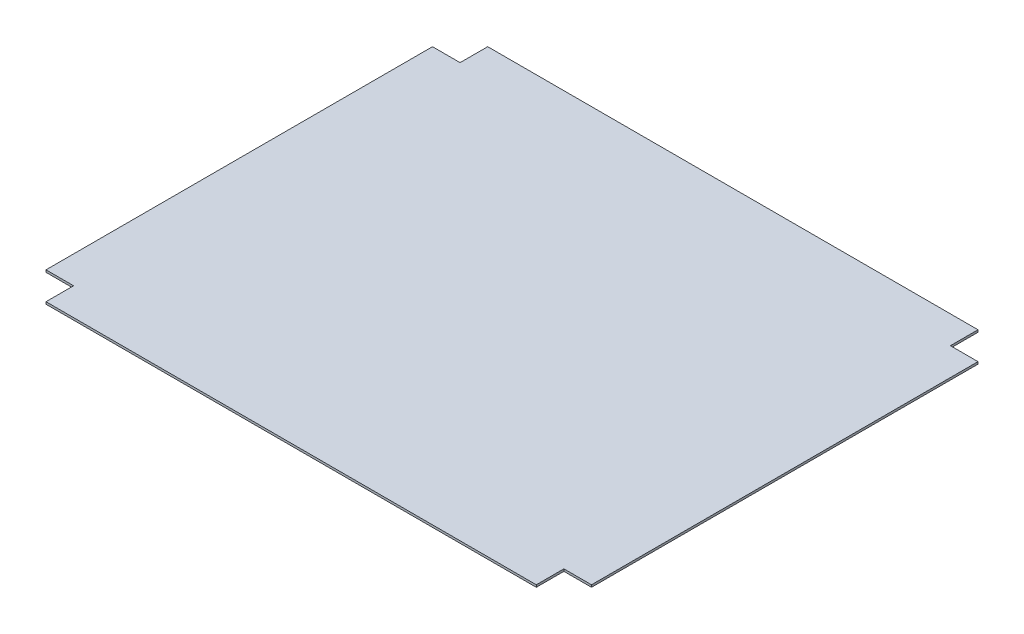
SolidWorks part; units mm, degrees
ref_plane "Ön Düzlem" through (0, 0, 0) normal (0, 0, 1) x (1, 0, 0)
ref_plane "Üst Düzlem" through (0, 0, 0) normal (0, 1, 0) x (1, 0, 0)
ref_plane "Sağ Düzlem" through (0, 0, 0) normal (1, 0, 0) x (0, 0, -1)
sketch "Çizim1" plane through (0, 0, 0) normal (0, 1, 0) x (1, 0, 0)
  line L1 (-247, 400) -> (247, 400)
  line L2 (-247, 400) -> (-247, 0)
  line L3 (-247, 0) -> (247, 0)
  line L4 (247, 400) -> (247, 0)
  point P4 (0, 0)
  dimension "D1" = 494
  dimension "D2" = 400
base flange "Taban-Flanş1" sketch "Çizim1" thickness 2 reverse thickness direction no parameters "D1"=0.7366
sketch "Çizim6" plane through (0, -2, 0) normal (0, -1, 0) x (1, 0, 0)
  line L0 (-247, -200) -> (-223.3794, -200) construction
  line L1 (-247, 0) -> (-222, 0)
  line L2 (-247, 0) -> (-247, -25)
  line L3 (-247, -25) -> (-222, -25)
  line L4 (-222, 0) -> (-222, -25)
  line L5 (-247, -400) -> (-247, 0) construction
  line L6 (0, 0) -> (0, -327.5766) construction
  line L7 (247, -25) -> (222, -25)
  line L8 (222, 0) -> (222, -25)
  line L9 (247, 0) -> (222, 0)
  line L10 (247, 0) -> (247, -25)
  line L11 (247, -400) -> (247, -375)
  line L12 (247, -400) -> (222, -400)
  line L13 (222, -400) -> (222, -375)
  line L14 (247, -375) -> (222, -375)
  line L15 (-247, -375) -> (-222, -375)
  line L16 (-222, -400) -> (-222, -375)
  line L17 (-247, -400) -> (-222, -400)
  line L18 (-247, -400) -> (-247, -375)
  dimension "D1" = 25
  dimension "D2" = 25
extrude "Kes-Ekstrüzyon1" cut sketch "Çizim6" against normal blind 10 normal cut yes
sketch "Büküm-Çizgileri1" [suppressed] plane through (0, 0, 0) normal (0, 1, 0) x (1, 0, 0)
sketch "Sınırlandırma-Kutusu1" [suppressed] plane through (0, 0, 0) normal (0, 1, 0) x (1, 0, 0)
sheet metal parameters "Sac-Levha1" thickness 2 parameters "D1"=0.7366
flat pattern "Düz-Çoğaltma1" [suppressed]
sketch "Büküm-Çizgileri2" plane through (0, 0, 0) normal (0, 1, 0) x (1, 0, 0)
sketch3d "Sınırlandırma-Kutusu2" [suppressed]
  line L0 (-453, 0, 0) -> (453, 0, 0) construction
  line L1 (-453, 400, 0) -> (453, 400, 0) construction
  line L2 (-453, 0, 0) -> (-453, 400, 0) construction
  line L3 (453, 0, 0) -> (453, 400, 0) construction
sheet metal parameters "Sac-Levha2" thickness 2 parameters "D1"=0.7366
flat pattern "Düz-Çoğaltma1"
sketch "Büküm-Çizgileri2" plane through (0, 0, 0) normal (0, 1, 0) x (1, 0, 0)
sketch3d "Sınırlandırma-Kutusu2" [suppressed]
  line L0 (247, 0, 0) -> (-247, 0, 0) construction
  line L1 (247, 400, 0) -> (-247, 400, 0) construction
  line L2 (247, 0, 0) -> (247, 400, 0) construction
  line L3 (-247, 0, 0) -> (-247, 400, 0) construction
